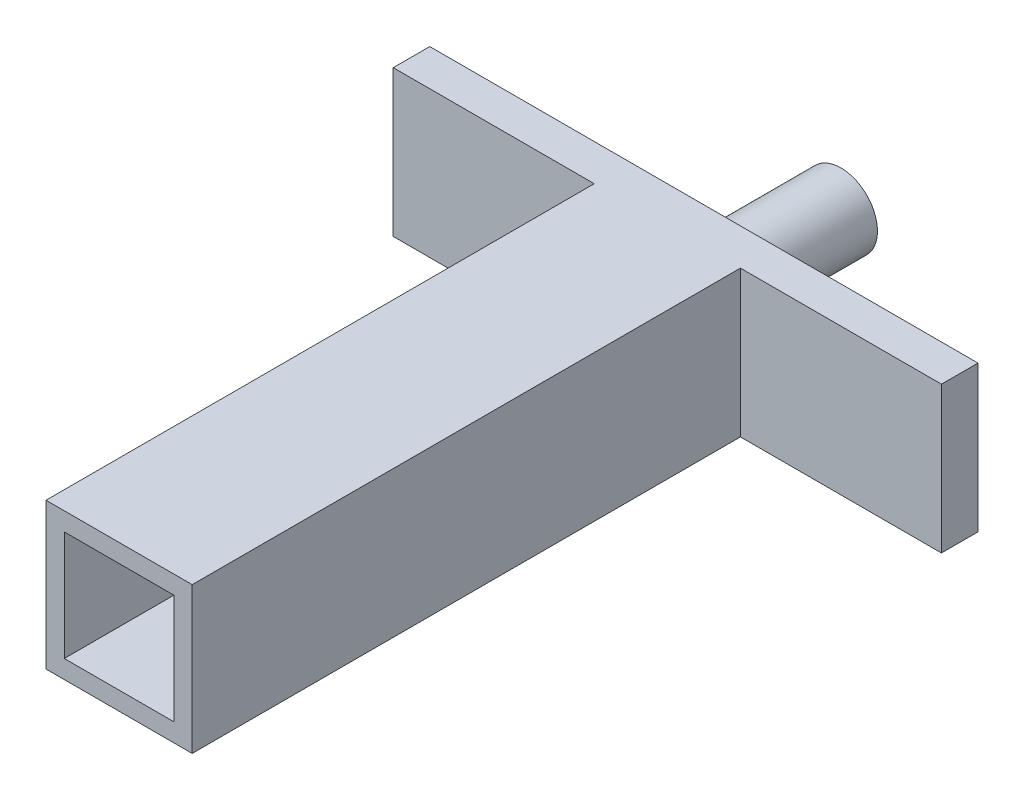
SolidWorks part; units mm, degrees
ref_plane "Front Plane" through (0, 0, 0) normal (0, 0, 1) x (1, 0, 0)
ref_plane "Top Plane" through (0, 0, 0) normal (0, 1, 0) x (1, 0, 0)
ref_plane "Right Plane" through (0, 0, 0) normal (1, 0, 0) x (0, 0, -1)
sketch "Эскиз8" plane through (0, 0, 0) normal (0, 0, 1) x (1, 0, 0)
  line L1 (-2, 2) -> (2, 2)
  line L2 (-2, 2) -> (-2, -2)
  line L3 (-2, -2) -> (2, -2)
  line L4 (2, 2) -> (2, -2)
  line L5 (-2, 2) -> (2, -2) construction
  line L6 (-2, -2) -> (2, 2) construction
  point P0 (0, 0)
  dimension "D1" = 4
  dimension "D2" = 4
extrude "Бобышка-Вытянуть5" add sketch "Эскиз8" along normal blind 16
shell "Оболочка2" thickness 0.5 removed face at (0, 0, 16)
sketch "Эскиз9" plane through (0, 0, 0) normal (0, 0, -1) x (-1, 0, 0)
  circle A0 centre (0, 0) radius 1
extrude "Бобышка-Вытянуть6" add sketch "Эскиз9" along normal blind 3.7
sketch "Эскиз10" plane through (0, 0, -3.7) normal (0, 0, -1) x (-1, 0, 0)
  line L0 (0, -0.5566) -> (0, 0.5566)
  arc A0 (0.1542, -0.6797) -> (0, -0.5566) centre (0.1263, -0.5566) cw
  circle A1 centre (0, 0) radius 1
  arc A2 (0.1542, 0.6797) -> (0.1542, -0.6797) centre (0, 0) cw
  arc A3 (0, 0.5566) -> (0.1542, 0.6797) centre (0.1263, 0.5566) cw
  circle A4 centre (0, 0) radius 0.849
  circle M1 centre (0, 0) radius 1
extrude "Бобышка-Вытянуть7" add sketch "Эскиз10" along normal blind 0.05 contours A4 M1 | A3 L0 A0 A2 region at (-0.2991, 0, -3.7) region at (0.9717, 0, -3.7)
sketch "Эскиз11" plane through (0, 0, 0) normal (0, 0, -1) x (-1, 0, 0)
  line L0 (-1, 0) -> (-7.5, 0) construction
  line L1 (-2, 2) -> (-7.5, 2)
  line L2 (-7.5, 2) -> (-7.5, -2)
  line L3 (-7.5, -2) -> (-2, -2)
  line L4 (0, 0) -> (0, 3.2725) construction
  line L5 (0, -0.5566) -> (0, 0.5566) construction
  line L6 (-2, 2) -> (-2, -2)
  line L7 (2, 2) -> (2, -2)
  line L8 (7.5, -2) -> (2, -2)
  line L9 (7.5, 2) -> (7.5, -2)
  line L10 (2, 2) -> (7.5, 2)
  circle A2 centre (0, 0) radius 1 construction
  circle A3 centre (0, 0) radius 1 construction
extrude "Бобышка-Вытянуть8" add sketch "Эскиз11" against normal blind 1
